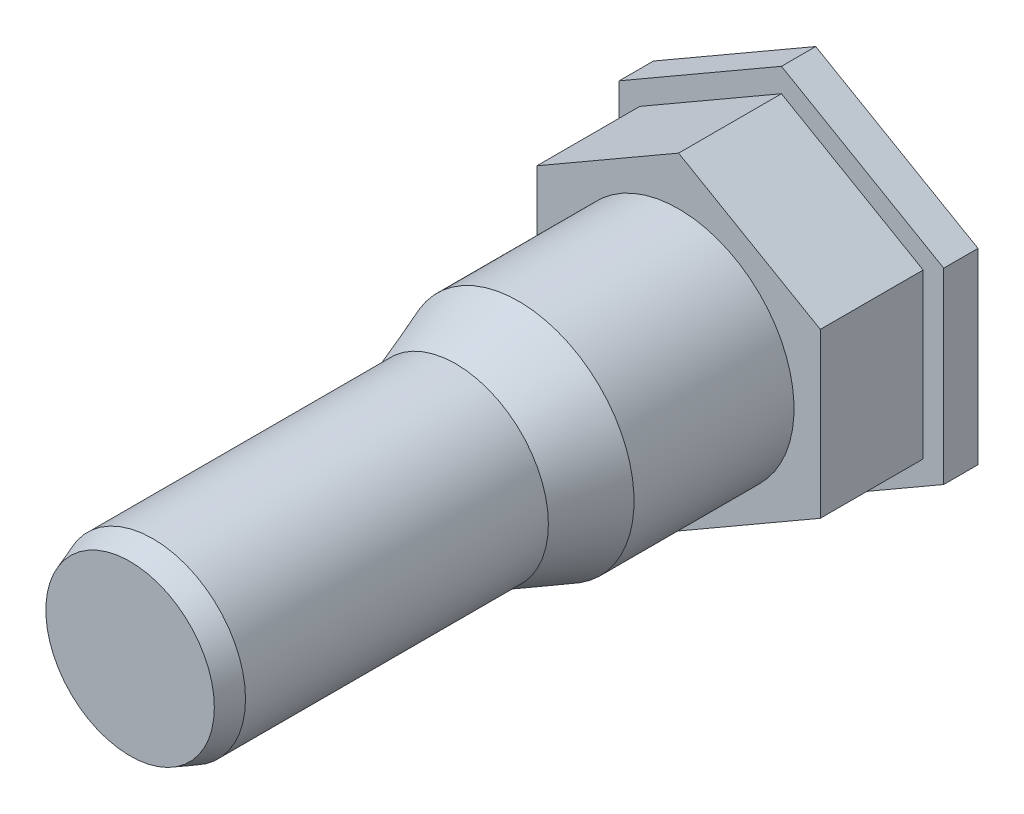
SolidWorks part; units mm, degrees
ref_plane "Front Plane" through (0, 0, 0) normal (0, 0, 1) x (1, 0, 0)
ref_plane "Top Plane" through (0, 0, 0) normal (0, 1, 0) x (1, 0, 0)
ref_plane "Right Plane" through (0, 0, 0) normal (1, 0, 0) x (0, 0, -1)
sketch "Sketch1" plane through (0, 0, 0) normal (0, 0, 1) x (1, 0, 0)
  line L12 (0, 7.1591) -> (6.2, 3.5796)
  line L14 (6.2, 3.5796) -> (6.2, -3.5796)
  line L15 (6.2, -3.5796) -> (0, -7.1591)
  line L16 (0, -7.1591) -> (-6.2, -3.5796)
  line L17 (-6.2, -3.5796) -> (-6.2, 3.5796)
  line L18 (-6.2, 3.5796) -> (0, 7.1591)
  line L19 (-7.1, 4.0992) -> (0, 8.1984)
  line L20 (0, 8.1984) -> (7.1, 4.0992)
  line L21 (7.1, 4.0992) -> (7.1, -4.0992)
  line L22 (7.1, -4.0992) -> (0, -8.1984)
  line L23 (0, -8.1984) -> (-7.1, -4.0992)
  line L24 (-7.1, -4.0992) -> (-7.1, 4.0992)
  circle A1 centre (0, 0) radius 3.05
  circle A2 centre (0, 0) radius 5.05
  circle A3 centre (0, 0) radius 2
  circle A4 centre (0, 0) radius 4.05
  point P3 (0, 7.1591)
  point P4 (6.2, 3.5796)
  point P7 (6.2, -3.5796)
  point P9 (0, -7.1591)
  point P10 (-6.2, -3.5796)
  point P12 (-6.2, 3.5796)
  point P13 (0, 0)
  dimension "D1" = 12.4
  dimension "D6" = 6.1
  dimension "D7" = 10.1
  dimension "D8" = 4
  dimension "D9" = 8.1
  dimension "D2" = 6
  dimension "D3" = 120
  dimension "D4" = 120
  dimension "D5" = 0.9
extrude "Boss-Extrude1" add sketch "Sketch1" along normal blind 1.5 contours L19 L20 L21 L22 L23 L24
ref_plane "Plane1" through (-7.1, -4.0992, 0) normal (-0.866, 0.5, 0) x (0, 0, 1)
ref_plane "Plane2" through (0, -8.1984, 0) normal (-0.866, 0.5, 0) x (0, 0, 1)
extrude "Boss-Extrude3" add sketch "Sketch1<8>" along normal blind 30 contours A4
sketch "Sketch1<8>" plane through (0, 0, 0) normal (0, 0, 1) x (1, 0, 0) same geometry as "Sketch1"
extrude "Boss-Extrude4" add sketch "Sketch1<9>" along normal blind 13 contours A2
sketch "Sketch1<9>" plane through (0, 0, 0) normal (0, 0, 1) x (1, 0, 0) same geometry as "Sketch1"
shell "Shell1" thickness 2
extrude "Cut-Extrude1" cut sketch "Sketch1<10>" along normal blind 11 contours A1
sketch "Sketch1<10>" plane through (0, 0, 0) normal (0, 0, 1) x (1, 0, 0) same geometry as "Sketch1"
extrude "Boss-Extrude2" add sketch "Sketch1<3>" along normal blind 6 contours L17 L18 L12 L14 L15 L16 | A1
sketch "Sketch1<3>" plane through (0, 0, 0) normal (0, 0, 1) x (1, 0, 0) same geometry as "Sketch1"
chamfer "Chamfer1" distance 1 angle 20 1 edges at (4.05, 0, 30) first distance on face at (4.05, 0, 13)
chamfer "Chamfer2" distance 1 angle 70 1 edges at (4.05, 0, 13) first distance on face at (4.05, 0, 13)
chamfer "Chamfer3" distance 0.6 angle 60 1 edges at (2.05, 0, 11) first distance on face at (2.05, 0, 11)
